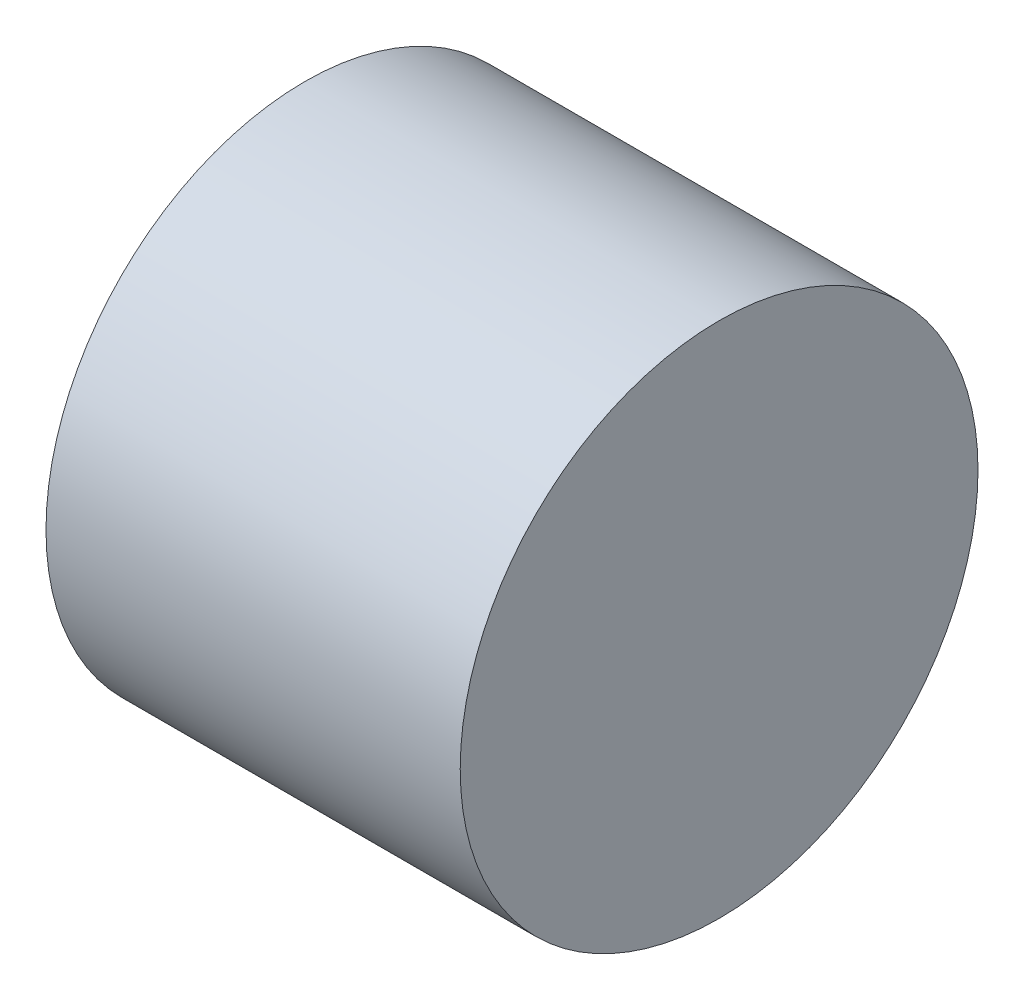
SolidWorks part; units mm, degrees
material "6061 Alloy"
ref_plane "Front Plane" through (0, 0, 0) normal (0, 0, 1) x (1, 0, 0)
ref_plane "Top Plane" through (0, 0, 0) normal (0, 1, 0) x (1, 0, 0)
ref_plane "Right Plane" through (0, 0, 0) normal (1, 0, 0) x (0, 0, -1)
sketch "Sketch1" plane through (0, 0, 0) normal (1, 0, 0) x (0, 0, -1)
  circle A0 centre (0, 0) radius 12.3825
  dimension "D1" = 24.765
extrude "Boss-Extrude1" add sketch "Sketch1" along normal mid plane 19.812 contours A0
